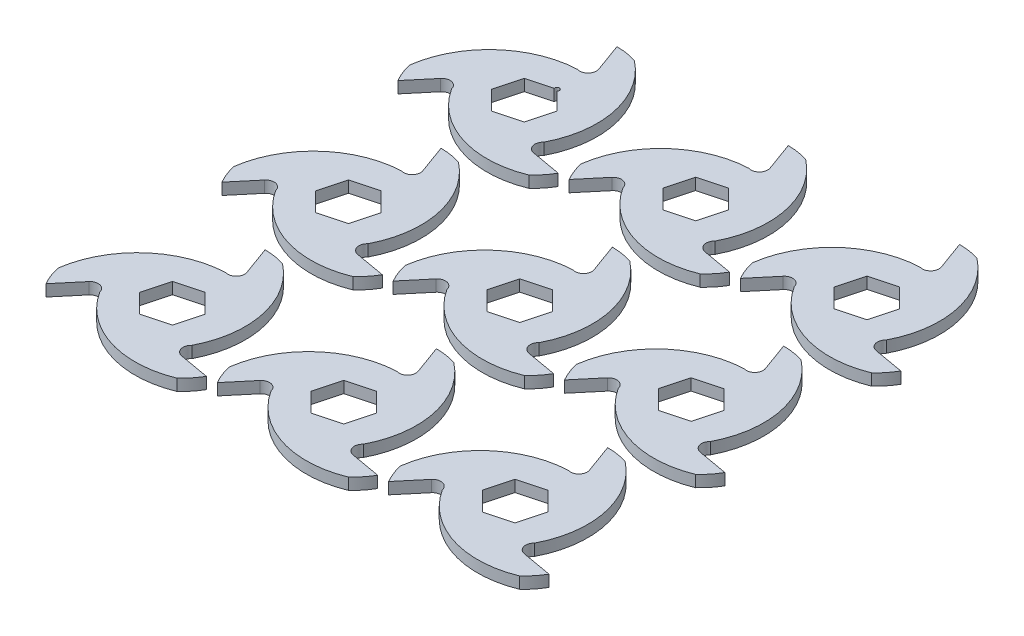
SolidWorks part; units mm, degrees
ref_plane "Front Plane" through (0, 0, 0) normal (0, 0, 1) x (1, 0, 0)
ref_plane "Top Plane" through (0, 0, 0) normal (0, 1, 0) x (1, 0, 0)
ref_plane "Right Plane" through (0, 0, 0) normal (1, 0, 0) x (0, 0, -1)
sketch "Sketch2" plane through (0, 0, 0) normal (0, 1, 0) x (1, 0, 0)
  line L0 (0, 50.8) -> (0, 0) construction
  line L1 (0, 0) -> (-43.9941, -25.4) construction
  line L2 (0, 0) -> (43.9941, -25.4) construction
  line L3 (0, 50.8) -> (5.6992, 35.1416)
  line L4 (43.9941, -25.4) -> (27.5839, -22.5064)
  line L5 (-43.9941, -25.4) -> (-33.2831, -12.6352)
  line L7 (3.7955, 14.165) -> (-10.3695, 10.3695)
  line L8 (-10.3695, 10.3695) -> (-14.165, -3.7955)
  line L9 (-14.165, -3.7955) -> (-3.7955, -14.165)
  line L10 (-3.7955, -14.165) -> (10.3695, -10.3695)
  line L11 (10.3695, -10.3695) -> (14.165, 3.7955)
  line L12 (14.165, 3.7955) -> (3.7955, 14.165)
  circle A0 centre (0, 0) radius 50.8 construction
  circle A1 centre (0, 13.2055) radius 37.5945
  circle A2 centre (11.4363, -6.6028) radius 37.5945
  circle A3 centre (-11.4363, -6.6028) radius 37.5945
  arc A4 (5.6992, 35.1416) -> (0, 29.21) centre (1.3938, 33.5746) cw
  arc A5 (27.5839, -22.5064) -> (25.2966, -14.605) centre (28.3796, -17.9943) cw
  arc A6 (-33.2831, -12.6352) -> (-25.2966, -14.605) centre (-29.7733, -15.5803) cw
  circle A7 centre (0, 0) radius 12.7 construction
  point P25 (0, 0)
  dimension "D1" = 101.6
  dimension "D4" = 20
  dimension "D6" = 15
  dimension "D2" = 120
  dimension "D3" = 120
  dimension "D5" = 21.59
  dimension "D8" = 25.4
  dimension "D7" = 3
extrude "Boss-Extrude2" add sketch "Sketch2" along normal mid plane 6.35 contours A1 A3 A2 L12 L11 L10 L9 L8 L7 | A1 A6 A2 A3 | L5 A6 A1 A3 | L4 A5 A3 A2 | A3 A5 A1 A2 | A2 A4 A3 A1 | L3 A4 A2 A1 region at (16.8055, 0, -37.817) region at (25.4344, 0, -14.5711) region at (-25.3361, 0, -14.7413) region at (-41.1532, 0, 4.3545) region at (18.3174, 0, -15.1298) region at (-0.0983, 0, 29.3123) region at (24.3477, 0, 33.4624)
sketch "Sketch3" plane through (0, 3.175, 0) normal (0, 1, 0) x (1, 0, 0)
  line L3 (43.9941, -25.4) -> (27.5839, -22.5064)
  line L4 (0, 50.8) -> (5.6992, 35.1416)
  line L5 (-43.9941, -25.4) -> (-33.2831, -12.6352)
  line L6 (43.9941, -25.4) -> (27.5839, -22.5064)
  line L7 (0, 50.8) -> (5.6992, 35.1416)
  line L8 (-43.9941, -25.4) -> (-33.2831, -12.6352)
  arc A0 (-48.1379, -14.7476) -> (0, 29.21) centre (2.2057, -21.5421) cw
  arc A1 (0, 29.21) -> (-43.9941, -25.4) centre (-11.4363, -6.6028) ccw construction
  arc A2 (0, 29.21) -> (5.6992, 35.1416) centre (1.3938, 33.5746) ccw construction
  arc A3 (11.2972, 49.0624) -> (25.2966, -14.605) centre (-19.7588, 8.8609) cw
  arc A4 (36.8407, -34.3148) -> (-25.2966, -14.605) centre (17.5532, 12.6812) cw
  arc A9 (-25.2966, -14.605) -> (-33.2831, -12.6352) centre (-29.7733, -15.5803) ccw
  arc A10 (-25.2966, -14.605) -> (43.9941, -25.4) centre (11.4363, -6.6028) ccw
  arc A11 (25.2966, -14.605) -> (27.5839, -22.5064) centre (28.3796, -17.9943) ccw
  arc A12 (25.2966, -14.605) -> (0, 50.8) centre (0, 13.2055) ccw
  arc A13 (0, 29.21) -> (5.6992, 35.1416) centre (1.3938, 33.5746) ccw
  arc A14 (0, 29.21) -> (-43.9941, -25.4) centre (-11.4363, -6.6028) ccw
  arc A15 (-25.2966, -14.605) -> (-33.2831, -12.6352) centre (-29.7733, -15.5803) ccw
  arc A16 (-25.2966, -14.605) -> (43.9941, -25.4) centre (11.4363, -6.6028) ccw
  arc A17 (25.2966, -14.605) -> (27.5839, -22.5064) centre (28.3796, -17.9943) ccw
  arc A18 (25.2966, -14.605) -> (0, 50.8) centre (0, 13.2055) ccw
  arc A19 (0, 29.21) -> (5.6992, 35.1416) centre (1.3938, 33.5746) ccw
  arc A20 (0, 29.21) -> (-43.9941, -25.4) centre (-11.4363, -6.6028) ccw
  point P26 (0, 0)
  arc M20 (-25.2966, -14.605) -> (43.9941, -25.4) centre (11.4363, -6.6028) ccw
  arc M23 (25.2966, -14.605) -> (0, 50.8) centre (0, 13.2055) ccw
  arc M26 (0, 29.21) -> (-43.9941, -25.4) centre (-11.4363, -6.6028) ccw
  dimension "D3" = 50.8
  dimension "D1" = 11.43
  dimension "D2" = 0
  dimension "D4" = 3
extrude "Cut-Extrude1" cut sketch "Sketch3" against normal through all contours A0 M26 | A3 M23 | A4 M20 region at (2.0677, 3.175, 36.1384) region at (30.2629, 3.175, -19.8599) region at (-32.3306, 3.175, -16.2785)
pattern_linear "LPattern1" count 3 spacing 96.52 along (0, 0, 1) count 3 spacing 93.98 along (1, 0, 0) of "Boss-Extrude2"
sketch "Sketch4" plane through (0, 3.175, 0) normal (0, 1, 0) x (1, 0, 0)
  circle A0 centre (3.7955, 14.165) radius 1.27
  dimension "D1" = 2.54
extrude "Cut-Extrude2" cut sketch "Sketch4" against normal through all
